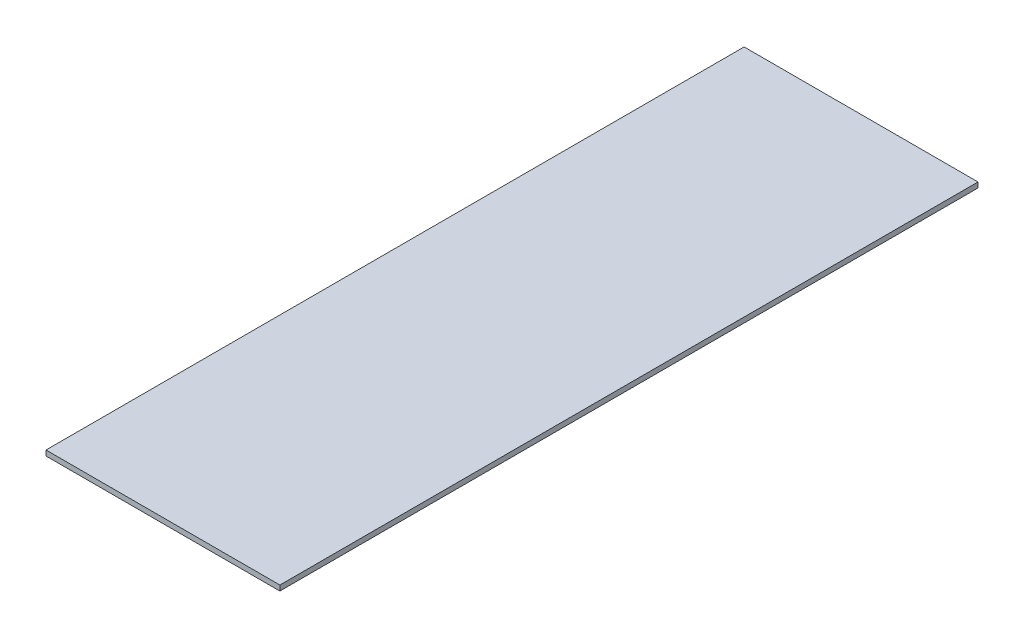
SolidWorks part; units mm, degrees
ref_plane "Front Plane" through (0, 0, 0) normal (0, 0, 1) x (1, 0, 0)
ref_plane "Top Plane" through (0, 0, 0) normal (0, 1, 0) x (1, 0, 0)
ref_plane "Right Plane" through (0, 0, 0) normal (1, 0, 0) x (0, 0, -1)
sketch "Sketch2" plane through (0, 0, 0) normal (0, 1, 0) x (1, 0, 0)
  line L1 (0, 0) -> (134, 0)
  line L2 (0, 0) -> (0, 400)
  line L3 (0, 400) -> (134, 400)
  line L4 (134, 0) -> (134, 400)
  dimension "D1" = 400
  dimension "D2" = 134
extrude "Boss-Extrude1" add sketch "Sketch2" along normal blind 3
